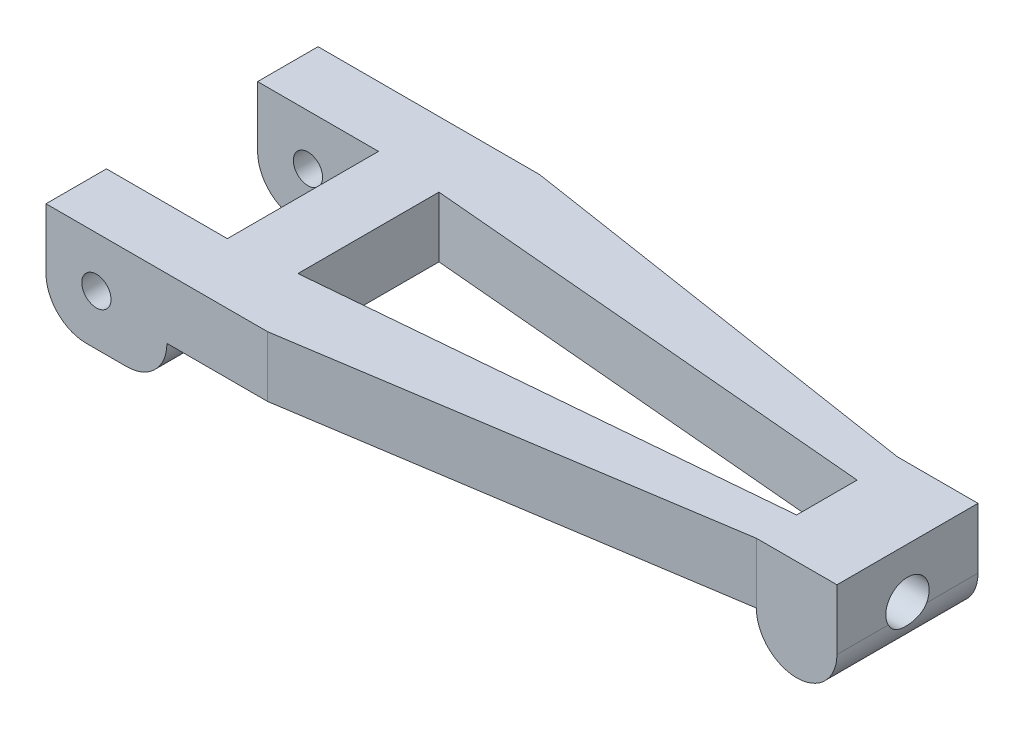
SolidWorks part; units mm, degrees
ref_plane "Front" through (0, 0, 0) normal (0, 0, 1) x (1, 0, 0)
ref_plane "Top" through (0, 0, 0) normal (0, 1, 0) x (1, 0, 0)
ref_plane "Right" through (0, 0, 0) normal (1, 0, 0) x (0, 0, -1)
sketch "Sketch1" plane through (0, 0, 0) normal (0, 1, 0) x (1, 0, 0)
  line L1 (0, 0) -> (72, 0)
  line L2 (0, 0) -> (0, -27)
  line L3 (0, -27) -> (72, -27)
  line L4 (72, 0) -> (72, -27)
  dimension "D1" = 27
  dimension "D2" = 72
extrude "Boss-Extrude1" add sketch "Sketch1" along normal blind 6
sketch "Sketch2" plane through (0, 6, 0) normal (0, 1, 0) x (1, 0, 0)
  line L0 (0, 0) -> (0, -27) construction
  line L1 (0, -21) -> (12, -21)
  line L2 (0, -21) -> (0, -6)
  line L3 (0, -6) -> (12, -6)
  line L4 (12, -21) -> (12, -6)
  dimension "D1" = 15
  dimension "D2" = 6
  dimension "D3" = 12
extrude "Cut-Extrude1" cut sketch "Sketch2" against normal through all
sketch "Sketch3" plane through (0, 0, 0) normal (0, -1, 0) x (-1, 0, 0)
  line L0 (-72, -27) -> (-72, 0) construction
  line L1 (-72, -20.5) -> (-64, -20.5)
  line L2 (-72, -20.5) -> (-72, -6.5)
  line L3 (-72, -6.5) -> (-64, -6.5)
  line L4 (-64, -20.5) -> (-64, -6.5)
  dimension "D1" = 14
  dimension "D2" = 8
  dimension "D3" = 6.5
extrude "Boss-Extrude2" add sketch "Sketch3" along normal blind 4
sketch "Sketch4" plane through (0, 0, 0) normal (0, -1, 0) x (-1, 0, 0)
  line L0 (-64, -20.5) -> (-22, -27)
  line L1 (0, -27) -> (-72, -27) construction
  line L2 (-22, -27) -> (-72, -27)
  line L3 (-72, -27) -> (-72, -20.5)
  line L4 (-72, -20.5) -> (-64, -20.5)
  line L5 (-64, -6.5) -> (-22, 0)
  line L6 (-72, 0) -> (0, 0) construction
  line L7 (-22, 0) -> (-72, 0)
  line L8 (-72, 0) -> (-72, -6.5)
  line L9 (-72, -6.5) -> (-64, -6.5)
  dimension "D1" = 50
  dimension "D2" = 50
extrude "Cut-Extrude2" cut sketch "Sketch4" against normal through all
sketch "Sketch5" plane through (0, 0, 0) normal (0, -1, 0) x (1, 0, 0)
  line L3 (0, 0) -> (12, 0)
  line L4 (0, 0) -> (0, 6)
  line L5 (0, 6) -> (12, 6)
  line L6 (12, 0) -> (12, 6)
  line L7 (0, 27) -> (12, 27)
  line L8 (0, 27) -> (0, 21)
  line L9 (0, 21) -> (12, 21)
  line L10 (12, 27) -> (12, 21)
extrude "Boss-Extrude3" add sketch "Sketch5" along normal blind 4
sketch "Sketch7" plane through (0, 0, 0) normal (0, -1, 0) x (-1, 0, 0)
  line L0 (-18.5, -20.5) -> (-18.5, -6.5)
  line L1 (-18.5, -6.5) -> (-64, -10.5)
  line L2 (-64, -20.5) -> (-64, -6.5) construction
  line L3 (-64, -10.5) -> (-64, -16.5)
  line L4 (-64, -16.5) -> (-18.5, -20.5)
  line L6 (-12, -27) -> (-22, -27) construction
  line L8 (-12, -21) -> (-12, -6) construction
  dimension "D1" = 14
  dimension "D2" = 6
  dimension "D3" = 4
  dimension "D4" = 6.5
  dimension "D5" = 6.5
extrude "Cut-Extrude4" cut sketch "Sketch7" against normal through all
sketch "Sketch8" plane through (72, 0, 0) normal (1, 0, 0) x (0, 0, -1)
  line L0 (-6.5, -4) -> (-6.5, 6) construction
  line L1 (-6.5, -4) -> (-20.5, -4) construction
  circle A0 centre (-13.5, 1) radius 2.15
  dimension "D1" = 4.3
  dimension "D2" = 7
  dimension "D3" = 5
extrude "Cut-Extrude5" cut sketch "Sketch8" against normal blind 10
sketch "Sketch9" plane through (0, 0, 0) normal (0, 0, -1) x (-1, 0, 0)
  line L0 (0, 6) -> (0, -4) construction
  line L1 (0, -4) -> (-12, -4) construction
  circle A0 centre (-5, 1) radius 1.45
  dimension "D1" = 2.9
  dimension "D2" = 5
  dimension "D3" = 5
extrude "Cut-Extrude6" cut sketch "Sketch9" against normal through all
fillet "Fillet2" radius 4 6 edges at (0, -4, 24) (0, -4, 3) (12, -4, 3) (12, -4, 24) (72, -4, 13.5) (64, -4, 13.5)
